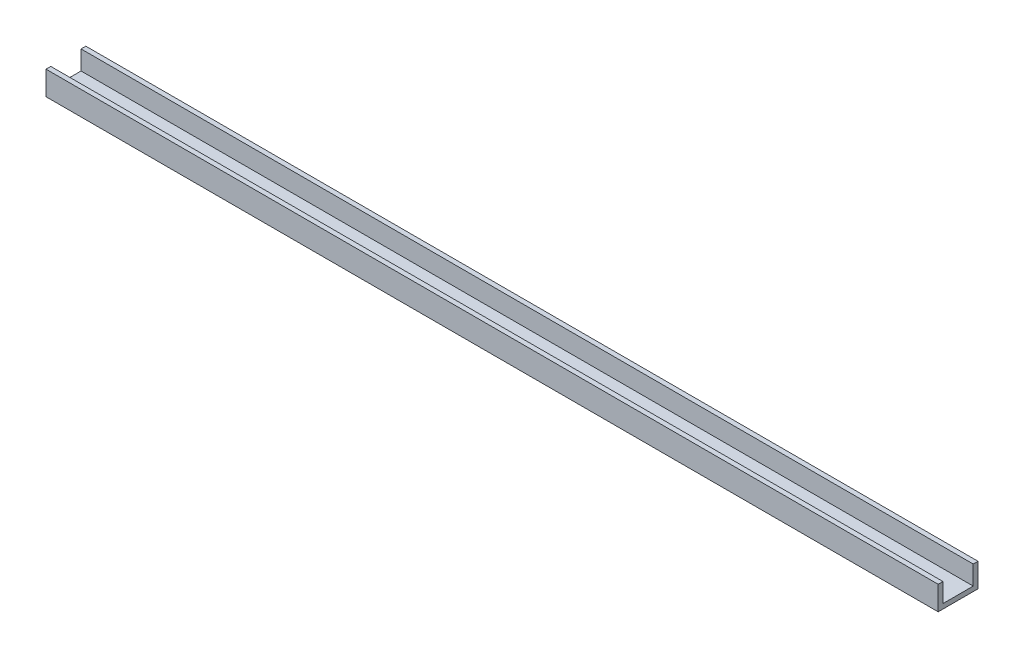
SolidWorks part; units mm, degrees
ref_plane "Спереди" through (0, 0, 0) normal (0, 0, 1) x (1, 0, 0)
ref_plane "Сверху" through (0, 0, 0) normal (0, 1, 0) x (1, 0, 0)
ref_plane "Справа" through (0, 0, 0) normal (1, 0, 0) x (0, 0, -1)
sketch "Эскиз1" plane through (0, 0, 0) normal (1, 0, 0) x (0, 0, -1)
  line L0 (-12.5, 0) -> (12.5, 0)
  line L1 (12.5, 0) -> (12.5, 15)
  line L2 (0, 29.661) -> (0, -35.101) construction
  line L3 (-12.5, 0) -> (-12.5, 15)
  point P8 (0, 0)
extrude "Вытянуть-Тонкостенный1" add sketch "Эскиз1" along normal blind 560 thin thin type one direction wall 3
